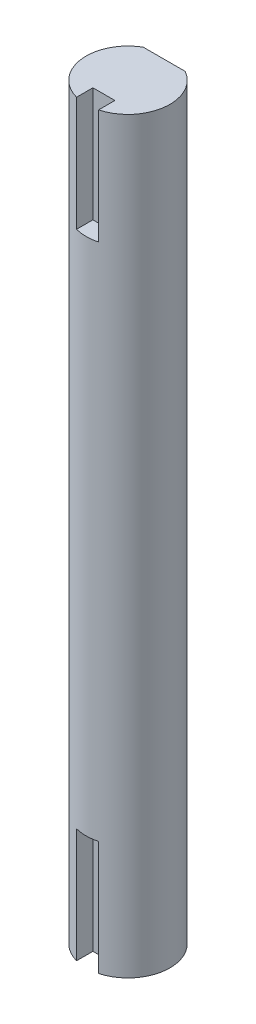
SolidWorks part; units mm, degrees
material "AISI 1045 Steel, cold drawn"
ref_plane "X-Y Datum" through (0, 0, 0) normal (0, 0, 1) x (1, 0, 0)
ref_plane "X-Z Datum" through (0, 0, 0) normal (0, 1, 0) x (1, 0, 0)
ref_plane "Y-Z Datum" through (0, 0, 0) normal (1, 0, 0) x (0, 0, -1)
sketch "Sketch1" plane through (0, 0, 0) normal (0, 1, 0) x (1, 0, 0)
  line L0 (-2.3876, 4.1208) -> (2.3876, 4.1208)
  circle A0 centre (0, 0) radius 4.7625
  dimension "D1" = 9.525
  dimension "D2" = 4.7752
extrude "Boss-Extrude1" add sketch "Sketch1" along normal blind 42.5 and the other way blind 42.5 contours L0 A0 region at (0, 0, 0.1312)
sketch "Sketch2" plane through (0, -42.5, 0) normal (0, -1, 0) x (1, 0, 0)
  line L0 (-1.25, 4.5955) -> (-1.25, 2.7375)
  line L1 (-1.25, 2.7375) -> (1.25, 2.7375)
  line L2 (1.25, 2.7375) -> (1.25, 4.5955)
  arc A0 (2.3876, -4.1208) -> (-2.3876, -4.1208) centre (0, 0) ccw construction
  circle A1 centre (0, 0) radius 4.7625 construction
  point P5 (0, -4.7625)
  point P8 (0, 2.7375)
  dimension "D1" = 2.5
  dimension "D2" = 7.5
extrude "Cut-Extrude1" cut sketch "Sketch2" against normal blind 13 and the other way through all
sketch "Sketch3" plane through (0, 42.5, 0) normal (0, 1, 0) x (1, 0, 0)
  line L0 (-1.25, -4.5955) -> (-1.25, -2.7375)
  line L1 (-1.25, -2.7375) -> (1.25, -2.7375)
  line L2 (1.25, -2.7375) -> (1.25, -4.5955)
  circle A0 centre (0, 0) radius 4.7625 construction
  arc A1 (-1.25, -4.5955) -> (1.25, -4.5955) centre (0, 0) ccw
  point P6 (0, -2.7375)
  point P9 (0, 4.7625)
  dimension "D1" = 2.5
  dimension "D2" = 7.5
extrude "Cut-Extrude2" cut sketch "Sketch3" against normal blind 13
